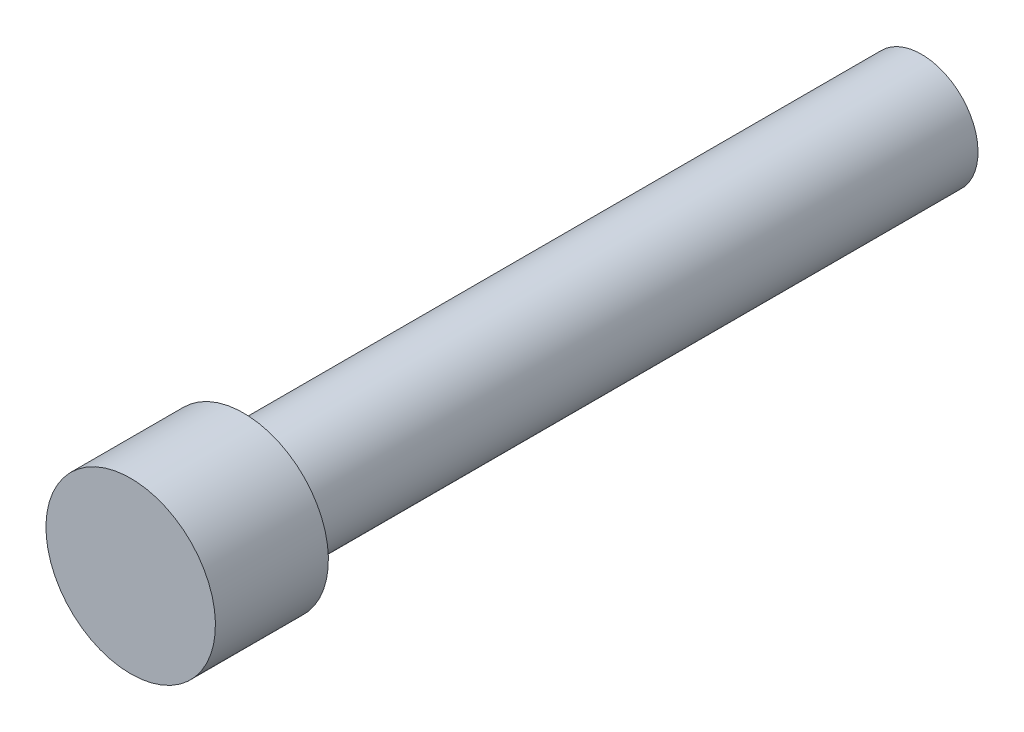
SolidWorks part; units mm, degrees
ref_plane "Front Plane" through (0, 0, 0) normal (0, 0, 1) x (1, 0, 0)
ref_plane "Top Plane" through (0, 0, 0) normal (0, 1, 0) x (1, 0, 0)
ref_plane "Right Plane" through (0, 0, 0) normal (1, 0, 0) x (0, 0, -1)
sketch "Sketch1" plane through (0, 0, 0) normal (1, 0, 0) x (0, 0, -1)
  line L0 (-22.225, 0) -> (22.225, 0) construction
  line L1 (-22.225, 0) -> (-22.225, 4.7625) construction
  line L2 (-22.225, 4.7625) -> (-15.875, 4.7625) construction
  line L3 (-15.875, 4.7625) -> (-15.875, 3.175) construction
  line L4 (-15.875, 3.175) -> (21.4001, 3.175) construction
  line L5 (22.1456, 3.3125) -> (22.7806, 2.2126) construction
  line L6 (22.7806, 2.2126) -> (23.4156, 3.3125) construction
  line L7 (23.4156, 3.3125) -> (22.1456, 3.3125) construction
  line L8 (21.4001, 3.175) -> (22.225, 2.3501) construction
  line L9 (22.225, 2.3501) -> (22.225, 0) construction
  line L10 (22.225, 3.175) -> (23.3363, 3.175) construction
  line L11 (22.7806, 3.3125) -> (22.7806, 3.175) construction
  line L12 (22.7806, 3.175) -> (22.7806, 2.3501) construction
  line L13 (22.7806, 2.3501) -> (22.7806, 2.2126) construction
  line L14 (22.7012, 2.3501) -> (22.86, 2.3501) construction
  line L15 (22.1853, 3.2437) -> (23.3759, 3.2437) construction
  line L16 (22.86, 2.3501) -> (23.3759, 3.2437) construction
  line L17 (22.7012, 2.3501) -> (22.1853, 3.2437) construction
  line L18 (-22.225, 2.3813) -> (-19.05, 2.3813) construction
  line L19 (-19.05, 2.3813) -> (-19.05, 0) construction
  line L20 (17.78, 3.175) -> (17.78, -3.175) construction
  point P20 (22.7806, 3.2437)
  point P22 (17.78, -3.175)
  point P28 (17.78, 0)
  point P29 (21.4001, -3.175)
  point P30 (-17.4625, 4.7625)
  point P31 (-11.5888, 0)
  point P33 (17.9387, 0)
  dimension "Length" = 38.1
  dimension "Head Height" = 6.35
  dimension "D1" = 45
  dimension "Thread Pitch" = 1.27
  dimension "D3" = 0.1588
  dimension "D4" = 4.445
  dimension "D5" = 3.175
  dimension "D2" = 4.7625
  dimension "Head Diameter" = 9.525
  dimension "Drive Size" = 4.7625
  dimension "Screw Size Decimal Equivalent" = 6.35
  dimension "D6" = 4.2862
  dimension "D7" = 4.2862
sketch "Sketch3" plane through (0, 0, 0) normal (1, 0, 0) x (0, 0, -1)
  line L0 (-22.225, 4.7625) -> (-22.225, 0)
  line L3 (-22.225, 0) -> (22.225, 0)
  line L4 (22.225, 0) -> (22.225, 3.175)
  line L6 (22.225, 3.175) -> (-15.875, 3.175)
  line L7 (-15.875, 3.175) -> (-15.875, 4.7625)
  line L8 (-15.875, 4.7625) -> (-22.225, 4.7625)
  line L11 (-22.225, 4.7625) -> (-15.875, 4.7625) construction
  point P2 (0, 0)
  point P6 (0, 0)
  point P12 (0, 0)
  point P17 (0, 0)
  point P20 (0, 0)
  point P25 (0, 0)
  point P26 (0, 0)
  point P27 (0, 0)
  point P28 (0, 0)
  point P33 (-15.875, 3.175)
revolve "Revolve1" add sketch "Sketch3" angle 360 about L0
sketch "Sketch4" plane through (0, 0, 22.225) normal (0, 0, 1) x (1, 0, 0)
  line L1 (0, 2.7496) -> (-2.3812, 1.3748)
  line L2 (-2.3812, 1.3748) -> (-2.3812, -1.3748)
  line L3 (-2.3812, -1.3748) -> (0, -2.7496)
  line L4 (0, -2.7496) -> (2.3812, -1.3748)
  line L5 (2.3812, -1.3748) -> (2.3812, 1.3748)
  line L6 (2.3812, 1.3748) -> (0, 2.7496)
  circle A0 centre (0, 0) radius 2.3812 construction
extrude "Cut-Extrude1" [suppressed] cut sketch "Sketch4" against normal up to vertex
sketch "Sketch5" [suppressed] plane through (0, 0, 22.225) normal (0, 0, 1) x (1, 0, 0)
  circle A0 centre (0, 0) radius 2.7496
extrude "Cut-Extrude2" [suppressed] cut sketch "Sketch5" against normal up to next draft 45
sketch "Sketch10" [suppressed] plane through (0, 0, 19.05) normal (0, 0, 1) x (1, 0, 0)
  line L0 (2.3812, 1.3748) -> (2.3813, -1.3748) construction
  circle A0 centre (0, 0) radius 2.3812
extrude "Cut-Extrude3" [suppressed] cut sketch "Sketch10" against normal through all draft 60
sketch "Sketch6" [suppressed] plane through (0, 0, -22.225) normal (0, 0, -1) x (-1, 0, 0)
  circle A0 centre (0, 0) radius 3.175 construction
  circle A1 centre (0, 0) radius 3.175
curve "Helix/Spiral1" [suppressed] pitch 1.27 height 39.37 turns 31
ref_plane "Plane1" [suppressed] through (0, 0, 15.875) normal (0, 0, 1) x (1, 0, 0)
split "Split1" [suppressed] bodies to split 112
sketch "Sketch7" [suppressed] plane through (0, 0, 0) normal (1, 0, 0) x (0, 0, -1)
  line L0 (22.7012, 2.3501) -> (22.86, 2.3501)
  line L8 (22.1853, 3.2437) -> (23.3759, 3.2437)
  line L9 (23.3759, 3.2437) -> (22.86, 2.3501)
  line L10 (22.8071, 2.3501) -> (22.7542, 2.3501) construction
  line L11 (22.7012, 2.3501) -> (22.1853, 3.2437)
  line L12 (22.7012, 2.3501) -> (22.7542, 2.3501) construction
  line L13 (22.8071, 2.3501) -> (22.86, 2.3501) construction
  point P10 (22.86, 2.3501)
  point P13 (22.7012, 2.3501)
sweep "Cut-Sweep1" [suppressed] cut profiles "Sketch7" path "Helix/Spiral1"
sketch "Sketch11" [suppressed] plane through (0, 0, 0) normal (1, 0, 0) x (0, 0, -1)
  line L2 (-15.875, 3.175) -> (21.4001, 3.175) construction
  line L3 (-17.6752, 3.5719) -> (-15.875, 3.5719)
  line L4 (-14.605, 3.175) -> (-11.43, 0)
  line L5 (-22.225, 0) -> (22.225, 0) construction
  line L6 (-11.43, 0) -> (-15.875, 0)
  line L7 (-15.875, 0) -> (-15.875, 3.5719) construction
  line L9 (-17.6752, 3.5719) -> (-17.6752, 0)
  line L10 (-17.6752, 0) -> (-15.875, 0)
  line L11 (-15.875, 3.175) -> (-15.875, 4.7625) construction
  line L12 (-15.4781, 3.175) -> (-14.605, 3.175)
  line L16 (-15.875, -4.572) -> (-15.875, 4.572) construction
  arc A0 (-15.875, 3.5719) -> (-15.4781, 3.175) centre (-15.4781, 3.5719) ccw construction
  arc A1 (-15.875, 3.5719) -> (-15.4781, 3.175) centre (-15.4781, 3.5719) ccw
  dimension "D3" = 45
revolve "Revolve2" [suppressed] add sketch "Sketch11" angle 360 about L6
equation "\"D3@Sketch1\" = \"Thread Pitch@Sketch1\" / 8"
equation "\"D4@Sketch1\" = \"Thread Pitch@Sketch1\" * 3.5"
equation "\"D3@Helix/Spiral1\"=\"Length@Sketch1\" +( \"Thread Pitch@Sketch1\")"
equation "\"D4@Helix/Spiral1\" = \"Thread Pitch@Sketch1\""
equation "\"D5@Sketch1\"=\"Head Height@Sketch1\"*0.5"
equation "\"D2@Sketch1\"=\"Head Height@Sketch1\"*0.75"
equation "\"D1@Sketch11\"=\"Thread Pitch@Sketch1\""
equation "\"D7@Sketch1\"=\"Length@Sketch1\"*.1125"
equation "\"D6@Sketch1\"=\"D7@Sketch1\""
equation "\"D3@Sketch1\"=\"Thread Pitch@Sketch1\"/8"
